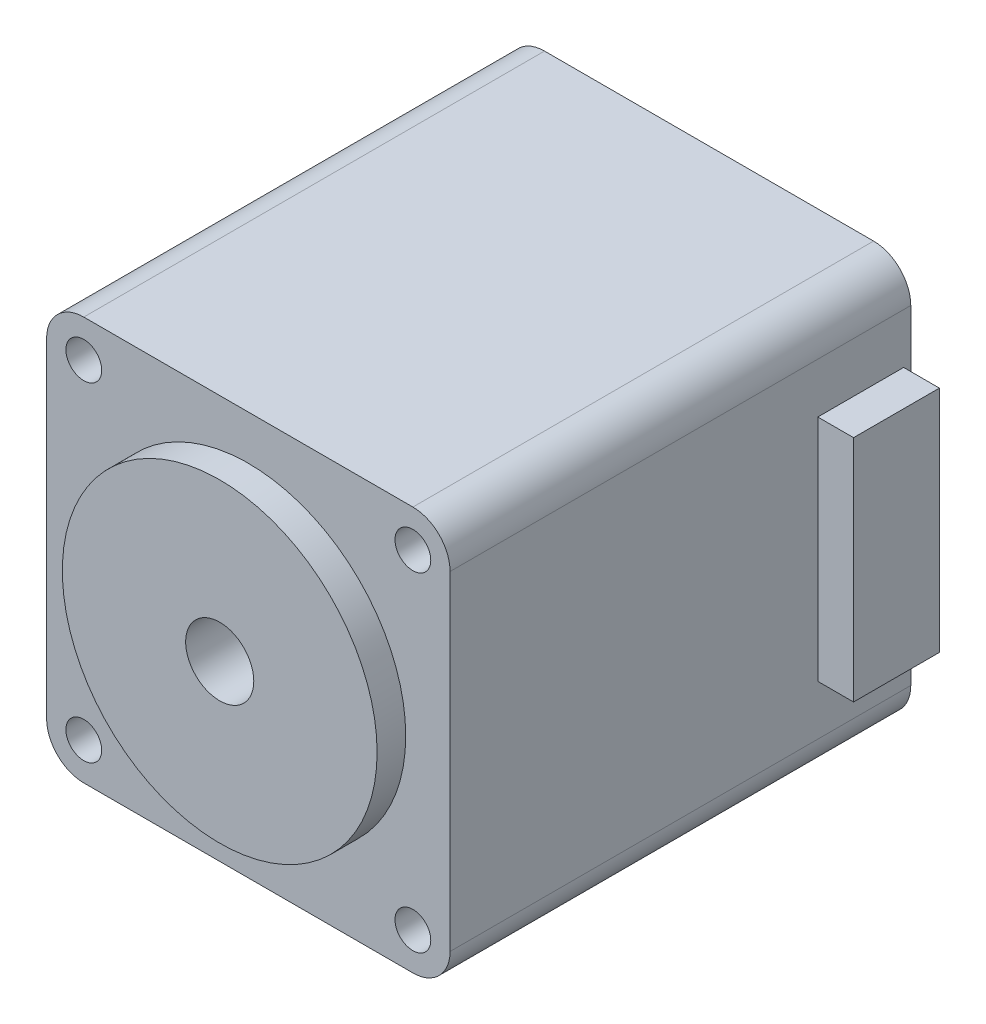
SolidWorks part; units mm, degrees
note: The reader was unsure of these and kept them because the rebuilt part matched: shared geometry of "Sketch1<3>", "Sketch1<4>", "Sketch1<5>".
ref_plane "Front Plane" through (0, 0, 0) normal (0, 0, 1) x (1, 0, 0)
ref_plane "Top Plane" through (0, 0, 0) normal (0, 1, 0) x (1, 0, 0)
ref_plane "Right Plane" through (0, 0, 0) normal (1, 0, 0) x (0, 0, -1)
sketch "Sketch1" plane through (0, 0, 0) normal (0, 0, 1) x (1, 0, 0)
  line L0 (14.1, -8) -> (16.6, -8)
  line L1 (11.5, 14.1) -> (-11.5, 14.1)
  line L2 (14.1, 11.5) -> (14.1, -11.5)
  line L3 (11.5, -14.1) -> (-11.5, -14.1)
  line L4 (-14.1, 11.5) -> (-14.1, -11.5)
  line L5 (14.1, 14.1) -> (-14.1, -14.1) construction
  line L6 (14.1, -14.1) -> (-14.1, 14.1) construction
  line L7 (16.6, -8) -> (16.6, 8)
  line L8 (16.6, 8) -> (14.1, 8)
  line L9 (14.1, 0) -> (16.6, 0) construction
  circle A0 centre (-11.5, 11.5) radius 1.25
  circle A1 centre (11.5, 11.5) radius 1.25
  circle A2 centre (11.5, -11.5) radius 1.25
  circle A3 centre (-11.5, -11.5) radius 1.25
  arc A4 (14.1, -11.5) -> (11.5, -14.1) centre (11.5, -11.5) cw
  arc A5 (11.5, 14.1) -> (14.1, 11.5) centre (11.5, 11.5) cw
  arc A6 (-11.5, 14.1) -> (-14.1, 11.5) centre (-11.5, 11.5) ccw
  arc A7 (-11.5, -14.1) -> (-14.1, -11.5) centre (-11.5, -11.5) cw
  circle A8 centre (0, 0) radius 11
  circle A9 centre (0, 0) radius 2.38
  point P0 (0, 0)
  point P17 (0, 0)
  dimension "D2" = 2.5
  dimension "D5" = 2.6
  dimension "D6" = 22
  dimension "D9" = 4.76
  dimension "D1" = 28.2
  dimension "D4" = 23
  dimension "D7" = 16
  dimension "D8" = 2.5
  dimension "D3" = 4
extrude "Boss-Extrude1" add sketch "Sketch1" along normal blind 32.2 contours A8 A9 | A7 L3 A4 L2 A5 L1 A6 L4 A8 A3 A2 A1 A0 | A2 | A3 | A0 | A9
extrude "Boss-Extrude2" add sketch "Sketch1<3>" along normal blind 6 from offset 0.5 contours L7 L8 L2 L0
sketch "Sketch1<3>" plane through (0, 0, 0) normal (0, 0, 1) x (1, 0, 0) same geometry as "Sketch1"
extrude "Cut-Extrude1" cut sketch "Sketch1<4>" against normal blind 2 from surface at 32.2 contours A0 | A1 | A2 | A3 starting at face at (0, 0, 32.2)
sketch "Sketch1<4>" plane through (0, 0, 0) normal (0, 0, 1) x (1, 0, 0) same geometry as "Sketch1"
extrude "Boss-Extrude3" add sketch "Sketch1<5>" along normal blind 2 from surface at 32.2 contours A8 A9 starting at face at (-10.25, -11.5, 32.2)
sketch "Sketch1<5>" plane through (0, 0, 0) normal (0, 0, 1) x (1, 0, 0) same geometry as "Sketch1"
sketch "Sketch2" plane through (0, 0, 0) normal (0, 1, 0) x (1, 0, 0)
  line L0 (0, 38.92) -> (0, -161.08)
  line L2 (-2.38, -154.2) -> (-2.38, 38.92)
  line L3 (-2.38, 38.92) -> (0, 38.92)
  line L4 (-11, -34.2) -> (11, -34.2) construction
  line L9 (0, -161.08) -> (-1.5, -161.08)
  line L10 (-1.5, -161.08) -> (-1.5, -155.08)
  line L11 (-1.5, -155.08) -> (-2.38, -154.2)
  dimension "D1" = 2.38
  dimension "D2" = 135
  dimension "D3" = 1.5
  dimension "D4" = 6
  dimension "D5" = 200
  dimension "D6" = 120
equation "\"D3@Sketch2\"=3/2"
